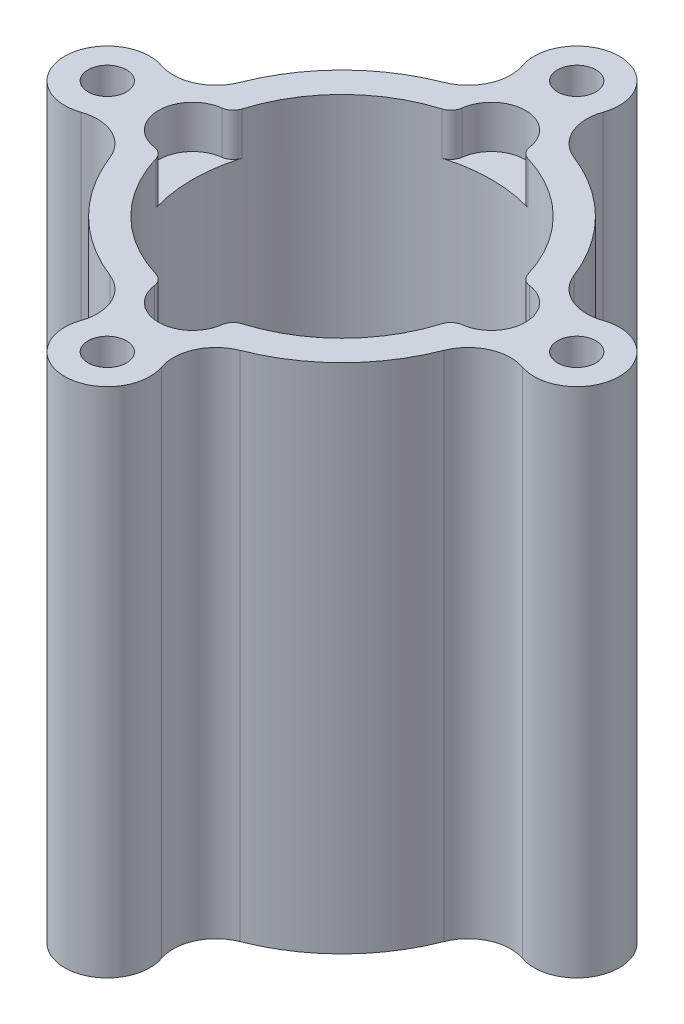
SolidWorks part; units mm, degrees
material "PLA"
ref_plane "正面" through (0, 0, 0) normal (0, 0, 1) x (1, 0, 0)
ref_plane "平面" through (0, 0, 0) normal (0, 1, 0) x (1, 0, 0)
ref_plane "右側面" through (0, 0, 0) normal (1, 0, 0) x (0, 0, -1)
sketch "ｽｹｯﾁ1" plane through (0, 0, 0) normal (0, 1, 0) x (1, 0, 0)
  line L0 (0, 0) -> (0, 27.5) construction
  circle A0 centre (0, 0) radius 27.5 construction
  circle A1 centre (0, 27.5) radius 2.25
  circle A2 centre (0, 0) radius 17.5
  circle A3 centre (27.5, 0) radius 2.25
  circle A4 centre (0, -27.5) radius 2.25
  circle A5 centre (-27.5, 0) radius 2.25
  arc A6 (4.7239, 25.8614) -> (-4.9793, 27.0455) centre (0, 27.5) ccw
  arc A7 (-7.6309, 19.5645) -> (-19.5645, 7.6309) centre (0, 0) ccw
  arc A8 (4.7239, 25.8614) -> (7.6309, 19.5645) centre (9.4477, 24.2227) ccw
  arc A9 (-4.7239, 25.8614) -> (-7.6309, 19.5645) centre (-9.4477, 24.2227) cw
  arc A10 (-4.7239, 25.8614) -> (4.9793, 27.0455) centre (0, 27.5) cw
  arc A11 (25.8614, 4.7239) -> (19.5645, 7.6309) centre (24.2227, 9.4477) cw
  arc A12 (25.8614, -4.7239) -> (19.5645, -7.6309) centre (24.2227, -9.4477) ccw
  arc A13 (25.8614, -4.7239) -> (27.0455, 4.9793) centre (27.5, 0) ccw
  arc A14 (25.8614, 4.7239) -> (27.0455, -4.9793) centre (27.5, 0) cw
  arc A15 (4.7239, -25.8614) -> (7.6309, -19.5645) centre (9.4477, -24.2227) cw
  arc A16 (-4.7239, -25.8614) -> (-7.6309, -19.5645) centre (-9.4477, -24.2227) ccw
  arc A17 (-4.7239, -25.8614) -> (4.9793, -27.0455) centre (0, -27.5) ccw
  arc A18 (4.7239, -25.8614) -> (-4.9793, -27.0455) centre (0, -27.5) cw
  arc A19 (-25.8614, -4.7239) -> (-19.5645, -7.6309) centre (-24.2227, -9.4477) cw
  arc A20 (-25.8614, 4.7239) -> (-19.5645, 7.6309) centre (-24.2227, 9.4477) ccw
  arc A21 (-25.8614, 4.7239) -> (-27.0455, -4.9793) centre (-27.5, 0) ccw
  arc A22 (-25.8614, -4.7239) -> (-27.0455, 4.9793) centre (-27.5, 0) cw
  arc A23 (-19.5645, -7.6309) -> (-7.6309, -19.5645) centre (0, 0) ccw
  arc A24 (7.6309, -19.5645) -> (19.5645, -7.6309) centre (0, 0) ccw
  arc A25 (19.5645, 7.6309) -> (7.6309, 19.5645) centre (0, 0) ccw
  point P15 (0, 0)
  point P52 (0, 0)
  dimension "D1" = 55
  dimension "D2" = 4.5
  dimension "D3" = 35
  dimension "D5" = 10
  dimension "D6" = 42
  dimension "D7" = 10
  dimension "D4" = 4
  dimension "D8" = 4
extrude "ﾎﾞｽ - 押し出し1" add sketch "ｽｹｯﾁ1" along normal blind 60 contours A11 A25 A8 A6 A10 A9 A7 A20 A21 A22 A19 A23 A16 A17 A18 A15 A24 A12 A13 A14 A1 A2 A3 A4 A5 region at (4.0735, 0, -21.7417)
sketch "ｽｹｯﾁ2" plane through (0, 60, 0) normal (0, 1, 0) x (1, 0, 0)
  line L0 (0, 0) -> (0, 17.5) construction
  arc A0 (-16.7632, 5.0246) -> (-16.7632, -5.0246) centre (0, 0) ccw construction
  arc A1 (3.9675, 18.0091) -> (-3.9675, 18.0091) centre (0, 17.5) ccw
  arc A5 (3.9675, 18.0091) -> (5.0246, 16.7632) centre (5.4553, 18.2) ccw
  arc A6 (-3.9675, 18.0091) -> (-5.0246, 16.7632) centre (-5.4553, 18.2) cw
  arc A7 (18.0091, -3.9675) -> (16.7632, -5.0246) centre (18.2, -5.4553) ccw
  arc A8 (18.0091, -3.9675) -> (18.0091, 3.9675) centre (17.5, 0) ccw
  arc A9 (18.0091, 3.9675) -> (16.7632, 5.0246) centre (18.2, 5.4553) cw
  arc A10 (-3.9675, -18.0091) -> (-5.0246, -16.7632) centre (-5.4553, -18.2) ccw
  arc A11 (-3.9675, -18.0091) -> (3.9675, -18.0091) centre (0, -17.5) ccw
  arc A12 (3.9675, -18.0091) -> (5.0246, -16.7632) centre (5.4553, -18.2) cw
  arc A13 (-18.0091, 3.9675) -> (-16.7632, 5.0246) centre (-18.2, 5.4553) ccw
  arc A14 (-18.0091, 3.9675) -> (-18.0091, -3.9675) centre (-17.5, 0) ccw
  arc A15 (-18.0091, -3.9675) -> (-16.7632, -5.0246) centre (-18.2, -5.4553) cw
  arc A16 (-16.7632, 5.0246) -> (-16.7632, -5.0246) centre (0, 0) ccw
  arc A17 (5.0246, 16.7632) -> (-5.0246, 16.7632) centre (0, 0) ccw construction
  arc A18 (5.0246, 16.7632) -> (-5.0246, 16.7632) centre (0, 0) ccw
  arc A19 (16.7632, -5.0246) -> (16.7632, 5.0246) centre (0, 0) ccw construction
  arc A20 (16.7632, -5.0246) -> (16.7632, 5.0246) centre (0, 0) ccw
  arc A21 (-5.0246, -16.7632) -> (5.0246, -16.7632) centre (0, 0) ccw construction
  arc A22 (-5.0246, -16.7632) -> (5.0246, -16.7632) centre (0, 0) ccw
  point P14 (0, 0)
  point P35 (0, 0)
  dimension "D1" = 35
  dimension "D2" = 8
  dimension "D4" = 3
extrude "ｶｯﾄ - 押し出し1" cut sketch "ｽｹｯﾁ2" against normal blind 5
